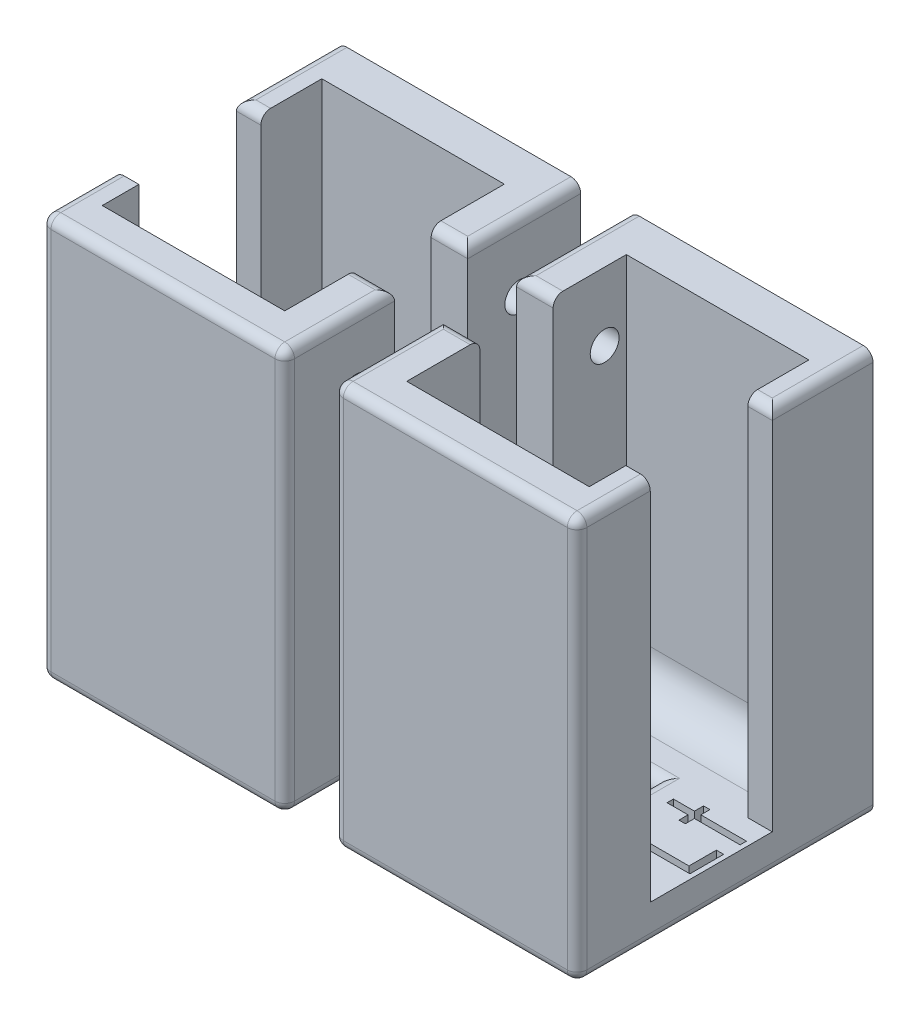
SolidWorks part; units mm, degrees
ref_plane "Front Plane" through (0, 0, 0) normal (0, 0, 1) x (1, 0, 0)
ref_plane "Top Plane" through (0, 0, 0) normal (0, 1, 0) x (1, 0, 0)
ref_plane "Right Plane" through (0, 0, 0) normal (1, 0, 0) x (0, 0, -1)
sketch "Sketch2" plane through (0, 0, 0) normal (0, 1, 0) x (1, 0, 0)
  line L0 (-9.5, -11.43) -> (9.5, -11.43)
  line L5 (12.04, -15.57) -> (-13.31, -15.57)
  line L10 (-13.31, -15.57) -> (-13.31, 15.24)
  line L15 (-13.31, 15.24) -> (12.04, 15.24)
  line L16 (12.04, 15.24) -> (12.04, 7.62)
  line L17 (12.04, -15.57) -> (12.04, -5.08)
  line L18 (12.04, 7.62) -> (9.5, 7.62)
  line L19 (9.5, 7.62) -> (9.5, 11.43)
  line L20 (9.5, 11.43) -> (-9.5, 11.43)
  line L21 (-9.5, 11.43) -> (-9.5, -11.43)
  line L22 (12.04, -5.08) -> (9.5, -5.08)
  line L24 (9.5, -11.43) -> (9.5, -5.08)
  point P6 (0, 11.43)
  point P12 (-9.5, 0)
  point P13 (0, 0)
  dimension "D1" = 22.86
  dimension "D2" = 19
  dimension "D3" = 3.81
  dimension "D4" = 3.81
  dimension "D5" = 7.62
  dimension "D6" = 2.54
  dimension "D7" = 5.08
  dimension "D8" = 4.14
extrude "Boss-Extrude2" add sketch "Sketch2" along normal blind 38.1
sketch "Sketch1" plane through (0, 0, 0) normal (0, 1, 0) x (1, 0, 0)
  line L1 (-13.31, -15.57) -> (12.04, -15.57)
  line L2 (-13.31, -15.57) -> (-13.31, 15.24)
  line L3 (-13.31, 15.24) -> (12.04, 15.24)
  line L4 (12.04, -15.57) -> (12.04, 15.24)
  point P0 (0, 0)
  point P6 (0, 0)
  point P8 (-13.31, -15.57)
extrude "Boss-Extrude3" add sketch "Sketch1" against normal blind 3.81
sketch "Sketch3" plane through (0, 0, 0) normal (0, 1, 0) x (1, 0, 0)
  line L1 (-1.88, -3.81) -> (1.12, -3.81)
  line L2 (-1.88, -3.81) -> (-1.88, 3.81)
  line L3 (-1.88, 3.81) -> (1.12, 3.81)
  line L4 (1.12, -3.81) -> (1.12, 3.81)
  line L5 (-9.5, -11.43) -> (-9.5, 11.43) construction
  point P6 (-1.88, 0)
  dimension "D1" = 7.62
  dimension "D2" = 3
  dimension "D3" = 7.62
extrude "Cut-Extrude1" cut sketch "Sketch3" against normal through all
sketch "Sketch4" plane through (-9.5, 0, 0) normal (1, 0, 0) x (0, 0, -1)
  line L0 (-11.43, 38.1) -> (11.43, 38.1) construction
  line L1 (-3.81, 38.1) -> (3.81, 38.1)
  line L2 (-3.81, 38.1) -> (-3.81, 8)
  line L3 (-3.81, 8) -> (3.81, 8)
  line L4 (3.81, 38.1) -> (3.81, 8)
  line L5 (-11.43, 0) -> (11.43, 0) construction
  line L6 (-11.43, 38.1) -> (11.43, 38.1) construction
  point P10 (0, 38.1)
  point P11 (0, 38.1)
  dimension "D1" = 8
  dimension "D2" = 7.62
extrude "Cut-Extrude2" cut sketch "Sketch4" against normal through all
sketch "Sketch5" plane through (-9.5, 0, 0) normal (1, 0, 0) x (0, 0, -1)
  line L1 (-11.43, 0) -> (11.43, 0) construction
  circle A0 centre (-9.17, 31) radius 1.5
  circle A1 centre (7.848, 31) radius 1.5
  dimension "D3" = 3
  dimension "D1" = 2.26
  dimension "D2" = 17.018
  dimension "D4" = 31
extrude "Cut-Extrude3" cut sketch "Sketch5" against normal through all
sketch "Sketch6" plane through (0, 0, 15.57) normal (0, 0, 1) x (1, 0, 0)
  line L0 (-13.31, 38.1) -> (-13.31, -3.81) construction
  line L3 (-1.88, -3.81) -> (-1.88, 0) construction
  line L8 (12.04, 38.1) -> (12.04, 0) construction
  line L11 (-13.31, 38.1) -> (-9.5, 38.1) construction
  circle A0 centre (-11.405, 19.05) radius 1.45
  circle A1 centre (-3.81, -1.905) radius 1.45
  point P2 (0, 0)
  point P4 (0, 0)
  point P7 (-13.31, 1.4331)
  point P9 (-1.88, -1.905)
  point P10 (0, 0)
  point P11 (0, 0)
  point P16 (0, 0)
  point P19 (0, 0)
  point P20 (-11.405, 38.1)
  point P22 (0, 0)
  point P23 (0, 0)
  point P26 (12.04, 19.05)
  dimension "D1" = 2.9
  dimension "D2" = 9.5
extrude "Cut-Extrude4" cut sketch "Sketch6" against normal offset from surface (25.984 mm away) 6.604 up to face at (-11.405, 23.05, -3.81) offset beyond the face yes
fillet "Fillet1" radius 4 2 edges at (0, 0, -11.43) (0, 0, 11.43)
mirror "Mirror1" about plane through (0, 0, 0) normal (0, 0, 1) of bodies 106 120
delete or keep bodies "Body-Delete/Keep 1" type keep bodies bodies 116
fillet "Fillet4" radius 2.54 2 edges at (-11.405, 8, -3.81) (-11.405, 8, 3.81)
fillet "Fillet2" radius 1.016 11 edges at (-0.635, -3.81, 15.24) (-13.31, 17.145, 15.24) (-0.635, 38.1, 15.24) (12.04, 17.145, 15.24) (-13.31, -3.81, -0.165) (12.04, -3.81, -0.165) (12.04, 38.1, 11.43) (-13.31, 38.1, 9.525) (-13.31, 38.1, -9.69) (-11.405, 38.1, -3.81) (-11.405, 38.1, 3.81)
fillet "Fillet3" radius 1.27 4 edges at (-0.38, 0, -3.81) (-1.88, 0, 0) (-0.38, 0, 3.81) (1.12, 0, 0)
fillet "Fillet5" radius 1.016 2 edges at (10.77, 38.1, -5.08) (12.04, 38.1, -10.325)
ref_plane "Plane1" through (-15.85, 0, 0) normal (-1, 0, 0) x (0, 0, 1)
mirror "Mirror3" about plane through (-15.85, 0, 0) normal (-1, 0, 0) of bodies 116 117 121
sketch "Sketch7" plane through (0, 0, 0) normal (0, 1, 0) x (1, 0, 0)
  line L0 (11.5383, -3.9427) -> (11.5383, 17.9144) construction
  text T0 "Lt\r\n" font "Century Gothic" height in points 28
extrude "Cut-Extrude5" cut sketch "Sketch7" against normal blind 1.27
sketch "Sketch8" plane through (0, 0, 0) normal (0, 1, 0) x (1, 0, 0)
  line L0 (-42.724, -6.0799) -> (-42.724, 4.0801) construction
  line L1 (-42.724, -14.224) -> (-42.724, -7.62) construction
  text T0 "Rt\r\n" font "Century Gothic" height in points 28
  dimension "D1" = 10.16
extrude "Cut-Extrude6" cut sketch "Sketch8" against normal blind 1.27
equation "\".30.83in\"=0.83"
